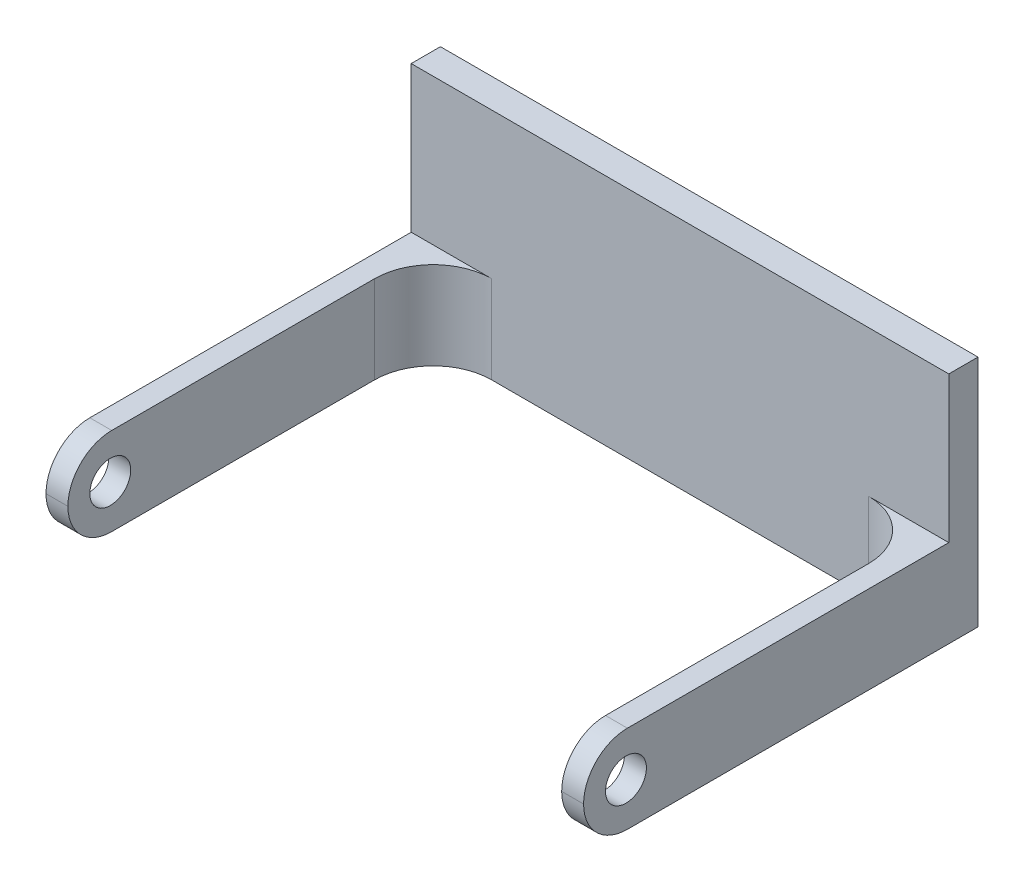
SolidWorks part; units mm, degrees
ref_plane "Front Plane" through (0, 0, 0) normal (0, 0, 1) x (1, 0, 0)
ref_plane "Top Plane" through (0, 0, 0) normal (0, 1, 0) x (1, 0, 0)
ref_plane "Right Plane" through (0, 0, 0) normal (1, 0, 0) x (0, 0, -1)
sketch "Sketch1" plane through (0, 0, 0) normal (0, 0, 1) x (1, 0, 0)
  line L1 (-18.4, -3) -> (18.4, -3)
  line L2 (-18.4, -3) -> (-18.4, 3)
  line L3 (-18.4, 3) -> (18.4, 3)
  line L4 (18.4, -3) -> (18.4, 3)
  line L5 (-18.4, -3) -> (18.4, 3) construction
  line L6 (-18.4, 3) -> (18.4, -3) construction
  point P0 (0, 0)
  dimension "D1" = 36.8
  dimension "D2" = 6
extrude "Boss-Extrude1" add sketch "Sketch1" along normal blind 2
sketch "Sketch2" plane through (0, 0, 2) normal (0, 0, 1) x (1, 0, 0)
  line L0 (-18.4, -3) -> (18.4, -3) construction
  line L1 (-18.4, 3) -> (-16.9, 3)
  line L2 (-18.4, 3) -> (-18.4, -3)
  line L3 (-18.4, -3) -> (-16.9, -3)
  line L4 (-16.9, 3) -> (-16.9, -3)
  line L6 (18.4, 3) -> (16.9, 3)
  line L7 (18.4, 3) -> (18.4, -3)
  line L8 (18.4, -3) -> (16.9, -3)
  line L9 (16.9, 3) -> (16.9, -3)
  dimension "D1" = 1.5
  dimension "D2" = 1.5
extrude "Boss-Extrude2" add sketch "Sketch2" along normal blind 25
sketch "Sketch3" plane through (18.4, 0, 0) normal (1, 0, 0) x (0, 0, -1)
  line L0 (-27, -3) -> (-27, 3) construction
  circle A0 centre (-24.1, 0) radius 1.4
  dimension "D1" = 2.8
  dimension "D2" = 2.9
extrude "Cut-Extrude1" cut sketch "Sketch3" against normal through all
fillet "Fillet1" radius 3 4 edges at (-17.65, -3, 27) (17.65, -3, 27) (-17.65, 3, 27) (17.65, 3, 27)
sketch "Sketch4" plane through (0, 3, 0) normal (0, 1, 0) x (1, 0, 0)
  line L0 (18.4, -24) -> (18.4, 0) construction
  line L1 (-18.4, 0) -> (18.4, 0)
  line L2 (-18.4, 0) -> (-18.4, -2)
  line L3 (-18.4, -2) -> (18.4, -2)
  line L4 (18.4, 0) -> (18.4, -2)
  dimension "D1" = 2
extrude "Boss-Extrude3" add sketch "Sketch4" along normal blind 10
fillet "Fillet2" radius 4 2 edges at (16.9, 0, 2)
